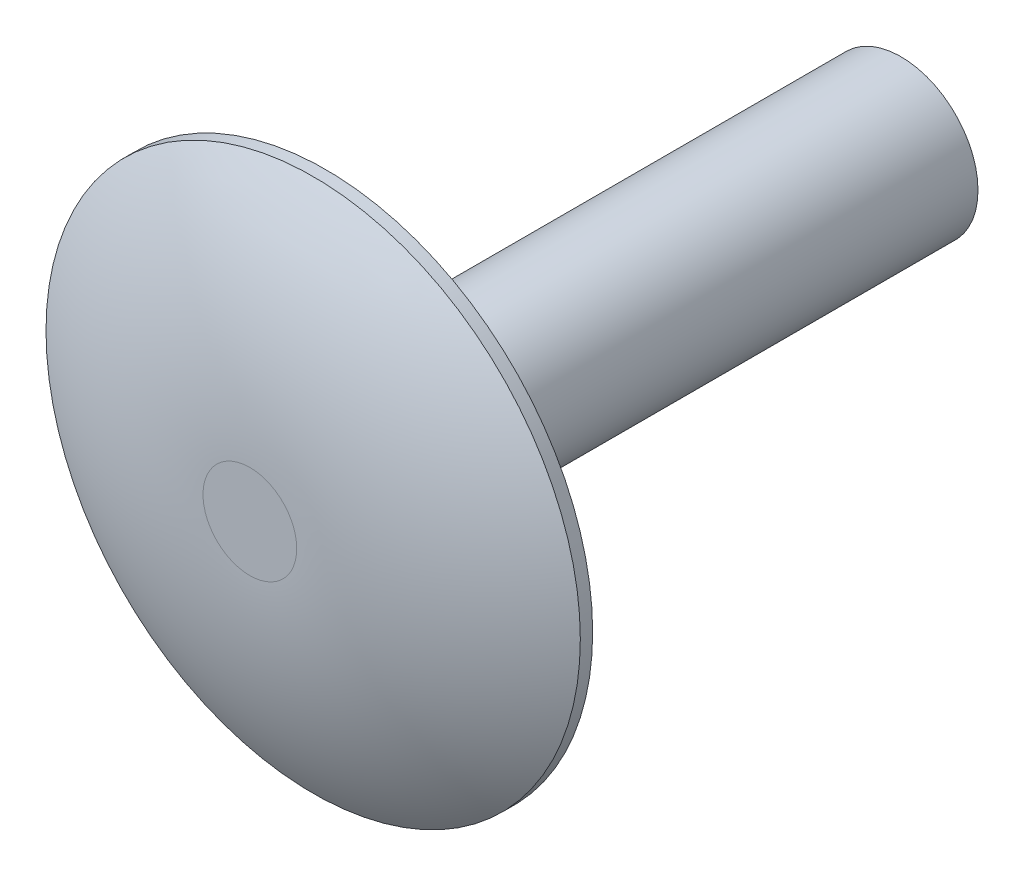
SolidWorks part; units mm, degrees
material "6061 Alloy"
ref_plane "Front Plane" through (0, 0, 0) normal (0, 0, 1) x (1, 0, 0)
ref_plane "Top Plane" through (0, 0, 0) normal (0, 1, 0) x (1, 0, 0)
ref_plane "Right Plane" through (0, 0, 0) normal (1, 0, 0) x (0, 0, -1)
sketch "Sketch1" plane through (0, 0, 0) normal (0, 0, 1) x (1, 0, 0)
  circle A0 centre (0, 0) radius 8.255
  dimension "D1" = 16.51
extrude "Boss-Extrude1" add sketch "Sketch1" along normal blind 2.3368
sketch "Sketch2" plane through (0, 0, 0) normal (0, 0, 1) x (1, 0, 0)
  circle A0 centre (0, 0) radius 2.3813
  dimension "D1" = 4.7625
extrude "Boss-Extrude2" add sketch "Sketch2" against normal blind 17.78
sketch "Sketch3" plane through (0, 0, 0) normal (0, 1, 0) x (1, 0, 0)
  line L0 (0, -2.3368) -> (1.4478, -2.3368)
  line L1 (-8.255, -2.3368) -> (8.255, -2.3368) construction
  line L2 (0, -2.3368) -> (0, 0) construction
  line L3 (8.255, -2.3368) -> (8.255, 0) construction
  line L4 (8.255, -0.381) -> (8.255, 0)
  line L5 (8.255, 0) -> (-8.255, 0) construction
  line L6 (8.255, -0.381) -> (8.255, -2.3368)
  line L7 (8.255, -2.3368) -> (1.4478, -2.3368)
  arc A0 (1.4478, -2.3368) -> (8.255, -0.381) centre (1.4478, 10.4874) ccw
  dimension "D1" = 2.8956
  dimension "D2" = 0.381
revolve "Cut-Revolve1" cut sketch "Sketch3" angle 360 about L2 region at (6.5802, 0, 1.7586)
